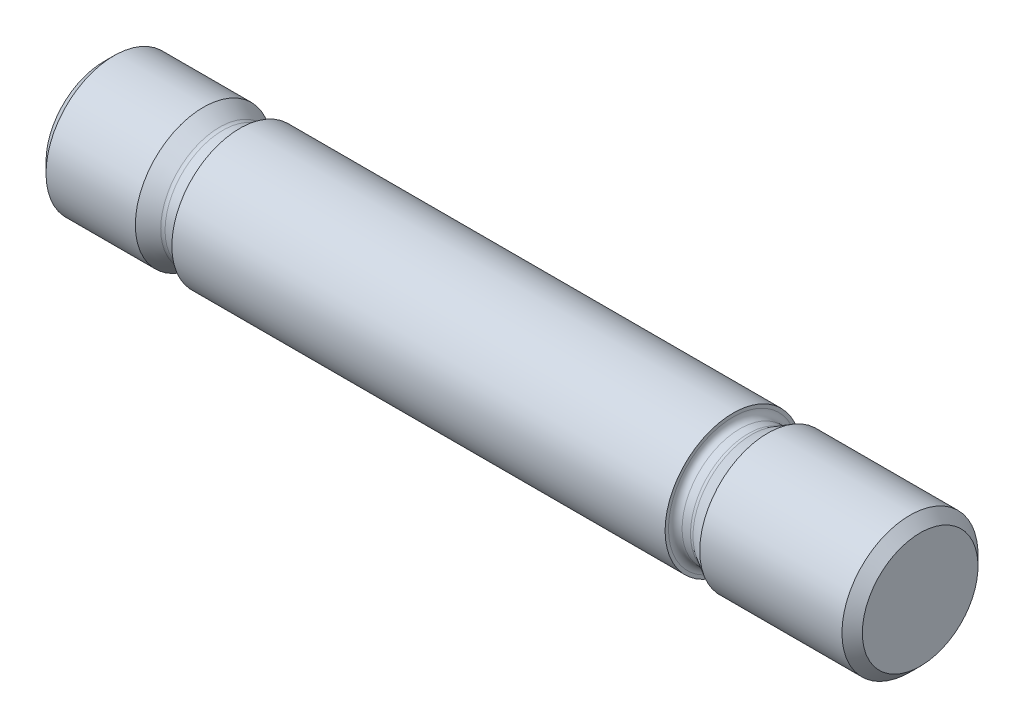
SolidWorks part; units mm, degrees
revolve "BaseBody" add sketch "BodySke" angle 360 about L14 other way angle 60
sketch "BodySke" plane through (0, 0, 0) normal (0, 0, 1) x (1, 0, 0)
  line L0 (17, 8.634) -> (14.634, 10)
  line L1 (14.634, 10) -> (1.5, 10)
  line L2 (20, 10) -> (20, 9.5)
  line L3 (19, 8.5) -> (17.5, 8.5)
  line L5 (1.5, 10) -> (0, 8.5)
  line L7 (92.5019, 10) -> (92.5019, 9.5)
  line L8 (93.5019, 8.5) -> (94.734, 8.5)
  line L9 (95.234, 8.634) -> (97.6, 10)
  line L10 (97.6, 10) -> (118.5, 10)
  line L11 (118.5, 10) -> (120, 8.5)
  line L12 (120, 8.5) -> (120, 0)
  line L13 (120, 0) -> (0, 0)
  line L14 (-3.175, 0) -> (101.6, 0) construction
  line L15 (99.7895, -8.5) -> (120, -8.5) construction
  line L16 (92.5019, -8.5) -> (95.0019, -8.5) construction
  line L17 (11.034, -10) -> (92.5019, -10) construction
  line L18 (0, 8.5) -> (0, 0)
  line L19 (20, 10) -> (92.5019, 10)
  line L20 (97.0019, 13.3514) -> (97.0019, -4.0014) construction
  line L21 (97.6, 12.2761) -> (97.6, -3.5735) construction
  arc A0 (17.5, 8.5) -> (17, 8.634) centre (17.5, 9.5) cw
  arc A1 (20, 9.5) -> (19, 8.5) centre (19, 9.5) cw
  arc A2 (94.734, 8.5) -> (95.234, 8.634) centre (94.734, 9.5) ccw
  arc A3 (92.5019, 9.5) -> (93.5019, 8.5) centre (93.5019, 9.5) ccw
  point P26 (95.0019, 8.5)
  point P29 (92.5019, 8.5)
  dimension "Advance" = 2
  dimension "Shoulder_neck_width" = 2.5
  dimension "Length" = 100
cosmetic thread "ThreadCosmetic" [suppressed] parameters "Thread_minor"=17
cosmetic thread "ThreadCosmeticStud" [suppressed] parameters "Thrd_minor"=17
ref_plane "Plane1" through (0, 0, 0) normal (0, 0, 1) x (1, 0, 0)
ref_plane "Plane2" through (0, 0, 0) normal (0, 1, 0) x (1, 0, 0)
ref_plane "Plane3" through (0, 0, 0) normal (1, 0, 0) x (0, 0, -1)
sketch "ThdSchSke" plane through (0, 0, 0) normal (0, 0, 1) x (1, 0, 0)
  line L0 (97.6, -8.5) -> (96.5497, -10)
  line L1 (97.6, -8.5) -> (98.6503, -10)
  line L2 (98.6503, -10) -> (98.6503, -12.5)
  line L3 (-3.175, 0) -> (5.1513, 0) construction
  line L4 (120, -8.5) -> (120, 8.5) construction
  line L5 (98.6503, -12.5) -> (96.5497, -12.5)
  line L6 (96.5497, -12.5) -> (96.5497, -10)
  dimension "Thread_minor" = 17
  dimension "Diameter" = 20
  dimension "Start" = 22.4
  dimension "SideAngle" = 55
  dimension "VeeAngle" = 70
  dimension "Overcut" = 25
revolve "ThreadSchematic" [suppressed] cut sketch "ThdSchSke" angle 360 about L3
pattern_linear "ThdSchPat" [suppressed]
sketch "ThdSchSketStud" plane through (0, 0, 0) normal (0, 0, 1) x (1, 0, 0)
  line L0 (15.5, -8.5) -> (14.4497, -10)
  line L1 (15.5, -8.5) -> (16.5503, -10)
  line L2 (16.5503, -10) -> (16.5503, -12.5)
  line L3 (-3.175, 0) -> (5.1513, 0) construction
  line L5 (16.5503, -12.5) -> (14.4497, -12.5)
  line L6 (14.4497, -12.5) -> (14.4497, -10)
  line L7 (0, 8.5) -> (0, -8.5) construction
  dimension "Thread_minor" = 17
  dimension "Diameter" = 20
  dimension "SideAngle" = 55
  dimension "VeeAngle" = 70
  dimension "Overcut" = 25
revolve "ThreadSchematicStud" [suppressed] cut sketch "ThdSchSketStud" angle 360 about L3
pattern_linear "ThdSchPatStud" [suppressed]
equation "\"Thread_minor@ThreadCosmetic\" = \"Minor_dia@BodySke\""
equation "\"Thrd_minor@ThreadCosmeticStud\" = \"Thread_minor@ThreadCosmetic\""
equation "\"Thread_len@BodySke\" = \"Thread_nom@BodySke\""
equation "\"Thread_minor@ThdSchSke\" = \"Minor_dia@BodySke\""
equation "\"Diameter@ThdSchSke\" = \"Thread_dia@BodySke\""
equation "\"Overcut@ThdSchSke\" = \"Thread_dia@BodySke\" * 1.25"
equation "\"Start@ThdSchSke\" = \"Thread_nom@BodySke\"  '   - \"Advance@BodySke\""
equation "\"Num_threads@ThdSchPat\" = int( \"Thread_len@BodySke\" / \"Advance@BodySke\" + 0.999 ) + 1"
equation "\"Advance@ThdSchPat\" = \"Thread_nom@BodySke\" /  ( \"Num_threads@ThdSchPat\" - 1 ) 'relax it"
equation "\"Num_threads@ThdSchPat\" = \"Num_threads@ThdSchPat\" - sgn( \"Num_threads@ThdSchPat\" - 1 ) '---chamfered tips only---"
equation "\"Diameter@ThdSchSketStud\" = \"Diameter@ThdSchSke\""
equation "\"Thread_minor@ThdSchSketStud\" = \"Thread_minor@ThdSchSke\""
equation "\"Overcut@ThdSchSketStud\" = \"Overcut@ThdSchSke\""
equation "\"Start_@ThdSchSketStud\" = \"Studend_length@BodySke\" - \"Shoulder_neck_width@BodySke\" - \"Advance@BodySke\""
equation "\"Num_threads@ThdSchPatStud\" = int( \"Start_@ThdSchSketStud\"/ \"Advance@BodySke\" + 0.999 )  + 1"
equation "\"Advance@ThdSchPatStud\" = \"Start_@ThdSchSketStud\" /  ( \"Num_threads@ThdSchPatStud\" - 1 ) 'relax it"
